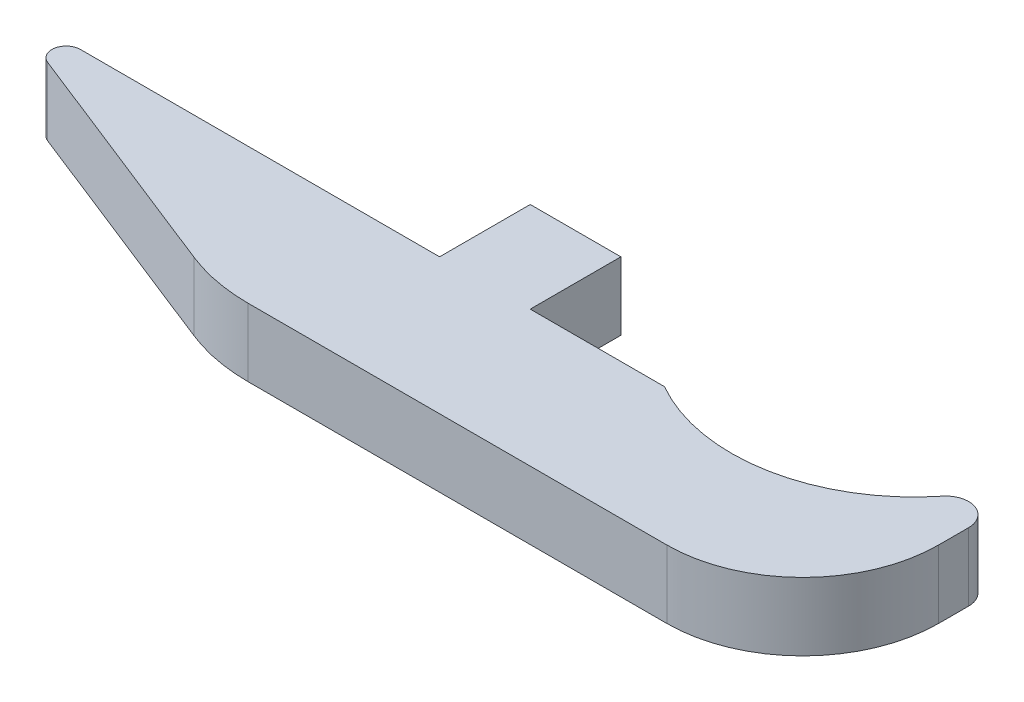
SolidWorks part; units mm, degrees
material "AISI 4130 Steel, annealed at 865C"
ref_plane "X-Y Datum" through (0, 0, 0) normal (0, 0, 1) x (1, 0, 0)
ref_plane "X-Z Datum" through (0, 0, 0) normal (0, 1, 0) x (1, 0, 0)
ref_plane "Y-Z Datum" through (0, 0, 0) normal (1, 0, 0) x (0, 0, -1)
sketch "Sketch1" plane through (0, 0, 0) normal (0, 1, 0) x (1, 0, 0)
  line L0 (20.8895, 0) -> (0, 0) construction
  line L1 (55.7276, 0) -> (0, 0)
  line L2 (55.7276, 0) -> (55.7276, 11.1252)
  line L3 (27.2796, -9.525) -> (68.5546, -9.525)
  line L4 (68.5546, 11.1252) -> (68.5546, -9.525)
  line L5 (3.175, 0) -> (27.2796, -9.525)
  circle A0 centre (55.7276, 11.1252) radius 12.827
  dimension "D3" = 25.654
  dimension "D5" = 9.525
  dimension "D1" = 55.7276
  dimension "D2" = 11.1252
  dimension "D4" = 3.175
  dimension "D6" = 41.275
extrude "Boss-Extrude1" add sketch "Sketch1" along normal blind 4.7625 contours L1 A0 region at (42.0539, 0, 4.2253)
fillet "Fillet1" radius 9.525 1 edges at (68.5546, 2.3813, 9.525)
fillet "Fillet2" radius 1.5875 1 edges at (68.5546, 2.3813, -11.1252)
fillet "Fillet4" radius 12.7 1 edges at (27.2796, 2.3813, 9.525)
sketch "Sketch2" plane through (0, 0, 0) normal (0, -1, 0) x (1, 0, 0)
  line L1 (39.9395, -6.35) -> (39.9395, 0)
  line L2 (-7.0505, -6.35) -> (27.8745, -6.35) construction
  line L3 (39.9395, 0) -> (33.5895, 0)
  line L4 (39.9395, 0) -> (39.9395, -6.35)
  line L5 (39.9395, -6.35) -> (33.5895, -6.35)
  line L6 (33.5895, 0) -> (33.5895, -6.35)
  line L7 (33.5895, 0) -> (33.5895, -6.35) construction
  line M6 (3.175, 0) -> (49.3431, 0)
  dimension "D1" = 6.35
  dimension "D2" = 6.35
extrude "Boss-Extrude2" add sketch "Sketch2" against normal blind 4.7625 contours L6 L5 L1 M6 region at (36.7645, 0, -3.175)
fillet "Fillet5" radius 1 1 edges at (3.175, 2.3813, 0)
